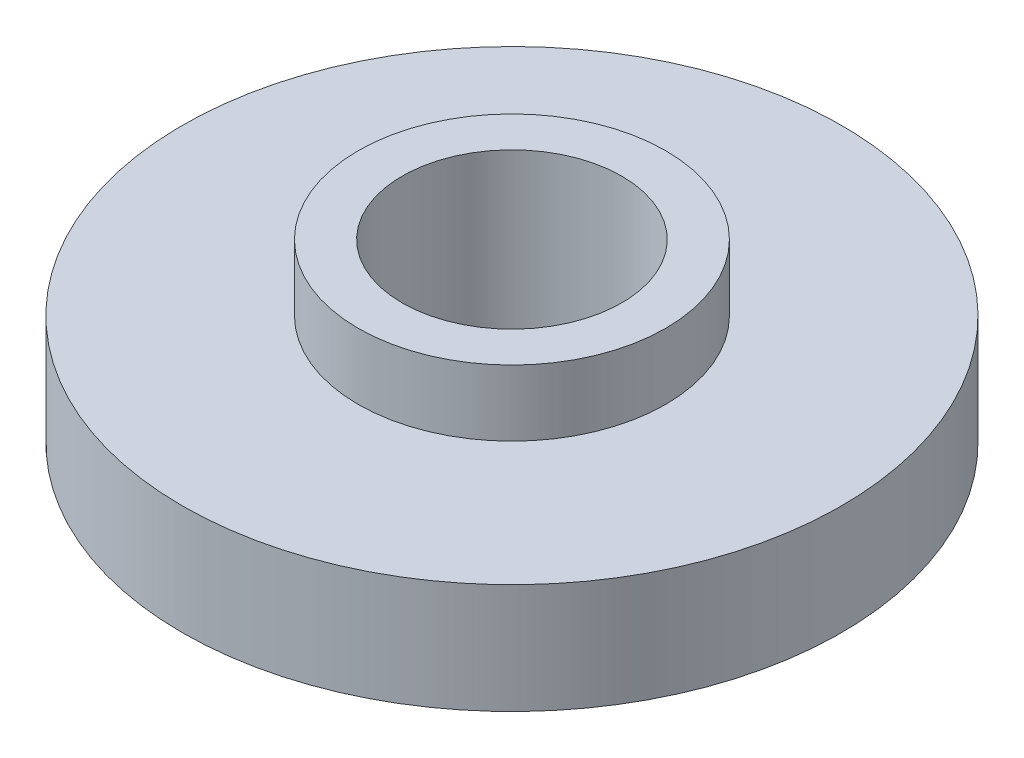
SolidWorks part; units mm, degrees
ref_plane "Front Plane" through (0, 0, 0) normal (0, 0, 1) x (1, 0, 0)
ref_plane "Top Plane" through (0, 0, 0) normal (0, 1, 0) x (1, 0, 0)
ref_plane "Right Plane" through (0, 0, 0) normal (1, 0, 0) x (0, 0, -1)
sketch "Sketch1" plane through (0, 0, 0) normal (0, 1, 0) x (1, 0, 0)
  circle A0 centre (0, 0) radius 3.5
  circle A1 centre (0, 0) radius 7.5
  circle A2 centre (0, 0) radius 2.5
  dimension "D1" = 7
  dimension "D2" = 15
extrude "Boss-Extrude2" add sketch "Sketch1" along normal blind 2.5 contours A1
extrude "Cut-Extrude1" cut sketch "Sketch1<6>" along normal blind 3.5 contours A2 region at (0, 0, 0)
sketch "Sketch1<6>" plane through (0, 0, 0) normal (0, 1, 0) x (1, 0, 0) same geometry as "Sketch1"
extrude "Boss-Extrude3" add sketch "Sketch1<7>" along normal blind 4 contours A0 A2 region at (-3.401, 0, 0)
sketch "Sketch1<7>" plane through (0, 0, 0) normal (0, 1, 0) x (1, 0, 0) same geometry as "Sketch1"
